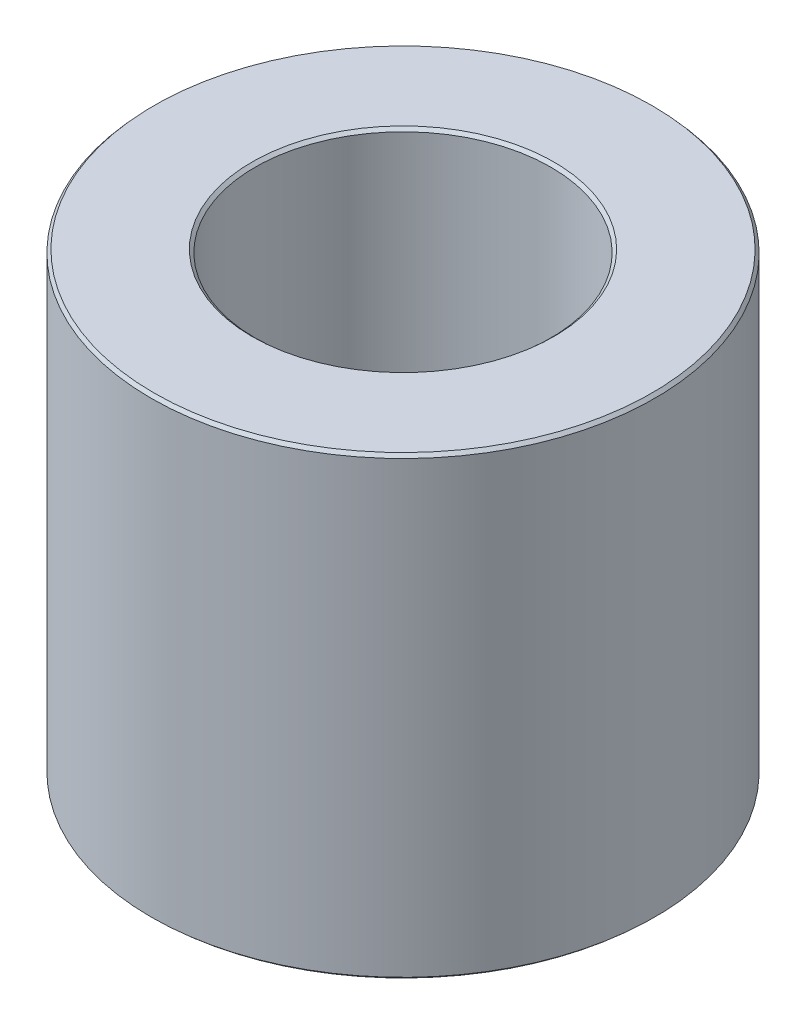
SolidWorks part; units mm, degrees
ref_plane "Front Plane" through (0, 0, 0) normal (0, 0, 1) x (1, 0, 0)
ref_plane "Top Plane" through (0, 0, 0) normal (0, 1, 0) x (1, 0, 0)
ref_plane "Right Plane" through (0, 0, 0) normal (1, 0, 0) x (0, 0, -1)
sketch "Sketch1" plane through (0, 0, 0) normal (0, 1, 0) x (1, 0, 0)
  circle A0 centre (0, 0) radius 17.5
  dimension "SLEEVE_OD" = 35
extrude "Boss-Extrude1" add sketch "Sketch1" along normal blind 31.6429
sketch "Sketch2" plane through (0, 0, 0) normal (0, 1, 0) x (1, 0, 0)
  circle A0 centre (0, 0) radius 10.2785
  dimension "BORE_D" = 20.557
extrude "Cut-Extrude1" cut sketch "Sketch2" along normal through all
chamfer "Chamfer1" distance 0.2215 angle 41.712 4 edges at (0, 31.6429, 10.2785) (0, 0, 10.2785) (0, 0, 17.5) (0, 31.6429, 17.5) first distance on face at (0, 31.6429, 10.2785) first distance on face at (0, 0, 10.2785) first distance on face at (0, 31.6429, 17.5)
